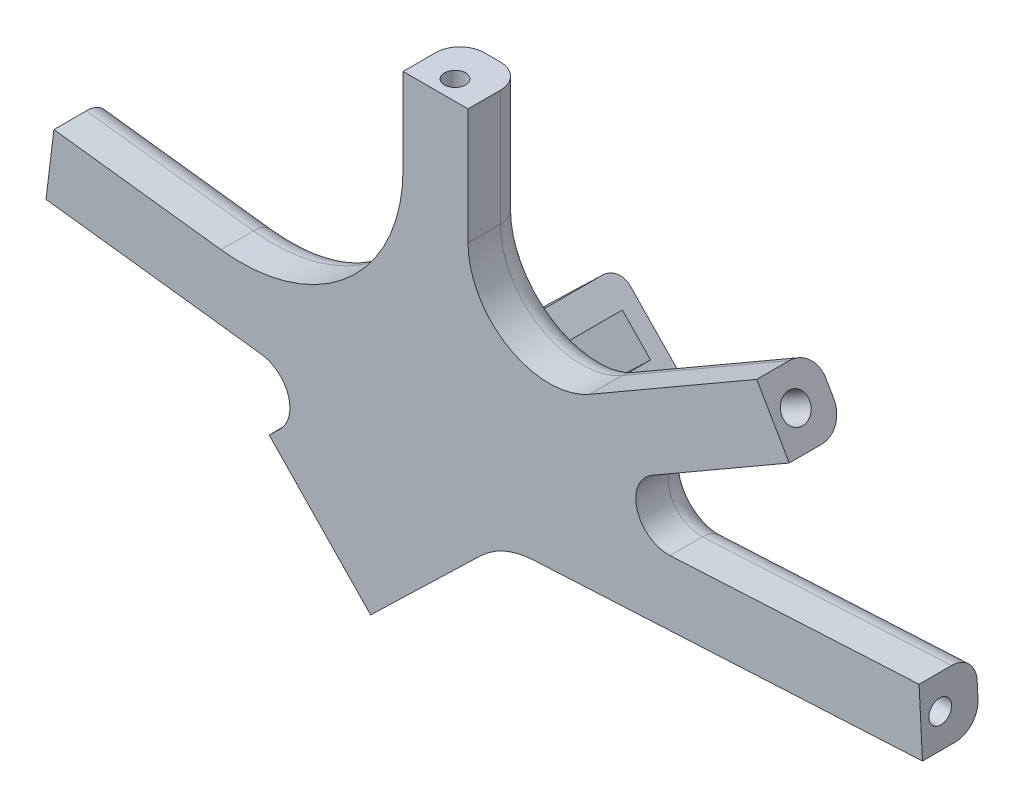
SolidWorks part; units mm, degrees
ref_plane "前基準面" through (0, 0, 0) normal (0, 0, 1) x (1, 0, 0)
ref_plane "上基準面" through (0, 0, 0) normal (0, 1, 0) x (1, 0, 0)
ref_plane "右基準面" through (0, 0, 0) normal (1, 0, 0) x (0, 0, -1)
sketch "草圖1" plane through (0, 0, 0) normal (0, 0, 1) x (1, 0, 0)
  line L0 (-27, 0) -> (-10.6362, 0) construction
  line L1 (-27, 3.1712) -> (-9.5687, 1.0309)
  line L2 (1.1225, -1.1562) -> (27, 0.2)
  line L3 (-27, 3.1712) -> (-26.5125, 7.1414)
  line L4 (-26.5125, 7.1414) -> (-5, 4.5)
  line L5 (3.1228, 2.9541) -> (26.7907, 4.1945)
  line L6 (26.7907, 4.1945) -> (27, 0.2)
  line L7 (-1, 5.1927) -> (16.7907, 15.4641)
  line L8 (16.7907, 15.4641) -> (18.7907, 12)
  line L9 (18.7907, 12) -> (3.1228, 2.9541)
  line L10 (-5, 4.5) -> (-5, 21)
  line L11 (-5, 21) -> (-1, 21)
  line L12 (-1, 21) -> (-1, 5.1927)
  line L13 (-9.5687, 1.0309) -> (-13.2519, -2.5259)
  line L14 (-13.2519, -2.5259) -> (-7, -9)
  line L15 (-7, -9) -> (1.1225, -1.1562)
  line L17 (2.3198, 0) -> (27, 0) construction
  point P19 (-10.6362, 0)
  dimension "D1" = 54
  dimension "D2" = 27
  dimension "D3" = 7
  dimension "D4" = 3
  dimension "D5" = 90
  dimension "D6" = 4
  dimension "D7" = 4
  dimension "D8" = 4.5
  dimension "D9" = 4
  dimension "D10" = 30
  dimension "D11" = 8
  dimension "D12" = 12
  dimension "D13" = 4
  dimension "D14" = 22
  dimension "D15" = 136
  dimension "D16" = 90
  dimension "D17" = 9
  dimension "D18" = 20
  dimension "D19" = 16.5
  dimension "D20" = 0.2
  dimension "D21" = 9
extrude "填料-伸長1" add sketch "草圖1" along normal blind 3.5
fillet "圓角1" radius 5 2 edges at (1.1225, -1.1562, 1.75) (-1, 5.1927, 1.75)
fillet "圓角2" radius 2 2 edges at (-9.5687, 1.0309, 1.75) (3.1228, 2.9541, 1.75)
fillet "圓角3" radius 10 1 edges at (-5, 4.5, 1.75)
sketch "草圖2" plane through (-26.9826, 3.313, 0) normal (-0.9925, 0.1219, 0) x (0, 0, 1)
  line L0 (3.5, 3.8571) -> (0, 3.8571) construction
  line L1 (3.5, 3.8571) -> (3.5, -0.1429) construction
  circle A0 centre (2.3, 1.8571) radius 0.65
  dimension "D1" = 1.3
  dimension "D2" = 2
  dimension "D3" = 1.2
extrude "除料-伸長1" cut sketch "草圖2" against normal blind 20
sketch "草圖3" plane through (0, 21, 0) normal (0, 1, 0) x (1, 0, 0)
  line L0 (-1, -3.5) -> (-1, 0) construction
  line L1 (-1, -3.5) -> (-5, -3.5) construction
  circle A0 centre (-3, -2.3) radius 0.65
  dimension "D2" = 1.3
  dimension "D1" = 2
  dimension "D3" = 1.2
extrude "除料-伸長2" cut sketch "草圖3" against normal blind 20
sketch "草圖4" plane through (19.2891, 11.1366, 0) normal (0.866, 0.5, 0) x (0, 0, -1)
  line L0 (-3.5, 4.997) -> (0, 4.997) construction
  line L1 (-3.5, 0.997) -> (-3.5, 4.997) construction
  circle A0 centre (-2.1, 2.997) radius 0.85
  point P2 (-1.75, 4.997)
  dimension "D2" = 1.7
  dimension "D1" = 2
  dimension "D3" = 1.4
extrude "除料-伸長3" cut sketch "草圖4" against normal blind 20
sketch "草圖5" plane through (26.9365, 1.4117, 0) normal (0.9986, 0.0523, 0) x (0, 0, -1)
  line L0 (0, 2.7867) -> (-3.5, 2.7867) construction
  line L1 (-3.5, -1.2133) -> (-3.5, 2.7867) construction
  circle A0 centre (-2.3, 0.7867) radius 0.7
  dimension "D2" = 1.4
  dimension "D1" = 2
  dimension "D3" = 1.2
extrude "除料-伸長4" cut sketch "草圖5" against normal blind 20
sketch "草圖6" plane through (0, 0, 0) normal (0, 0, -1) x (-1, 0, 0)
  line L0 (8.042, -7.921) -> (12.5573, -3.2453)
  line L1 (13.2519, -2.5259) -> (7, -9) construction
  line L2 (12.5573, -3.2453) -> (3.2058, 5.7853)
  line L3 (3.2058, 5.7853) -> (-1.3094, 1.1096)
  line L4 (-1.3094, 1.1096) -> (8.042, -7.921)
  line L6 (7, -9) -> (0.2222, -2.4548) construction
  line M17 (7, -9) -> (13.2519, -2.5259)
  dimension "D1" = 6.5
  dimension "D2" = 13
  dimension "D3" = 1.5
extrude "填料-伸長2" add sketch "草圖6" along normal blind 8 contours L3 L4 L2 M17 region at (-5.6239, -1.0679, 0)
sketch "草圖7" plane through (0.0774, -0.0802, 0) normal (0.6947, -0.7193, 0) x (0, 0, -1)
  line L0 (8, -11.2873) -> (0, -11.2873) construction
  circle A0 centre (4, -8.7873) radius 1
  circle A2 centre (4, -0.7873) radius 1
  dimension "D1" = 2
  dimension "D6" = 2
  dimension "D2" = 2.5
  dimension "D3" = 4
  dimension "D4" = 8
extrude "除料-伸長6" cut sketch "草圖7" against normal up to next
fillet "圓角5" radius 1.5 15 edges at (-12.9184, -2.2039, 0) (-12.0776, 0.1915, 0) (-21.3656, 6.5094, 0) (-5, 18.4015, 0) (-1, 17.4265, 0) (1.5, 9.5228, 0) (14.564, 9.5597, 0) (9.4196, 4.8194, 0) (-3.6111, -5.7274, 0) (1.2573, -1.4662, 0) (-20.3653, 2.3566, 0) (-8.3738, 8.3134, 0) (11.6453, 12.4934, 0) (19.1163, 3.7923, 0) (14.9947, -0.4292, 0)
sketch "草圖9" plane through (-8.1194, -7.8408, 0) normal (-0.7193, -0.6947, 0) x (0, 0, 1)
  line L1 (-7, 4.6386) -> (0, 4.6386)
  line L2 (-7, 4.6386) -> (-7, 2.1386)
  line L3 (-7, 2.1386) -> (0, 2.1386)
  line L4 (0, 4.6386) -> (0, 2.1386)
  line L5 (-7, 4.6386) -> (0, 2.1386) construction
  line L6 (-7, 2.1386) -> (0, 4.6386) construction
  line L7 (-8, 6.3886) -> (0, 6.3886) construction
  point P0 (-3.5, 3.3886)
  dimension "D1" = 2.5
  dimension "D2" = 7
  dimension "D3" = 7
  dimension "D4" = 1.75
extrude "除料-伸長8" cut sketch "草圖9" against normal blind 15
fillet "圓角6" radius 1 2 edges at (-3.3663, -3.4057, -8) (-7.8816, 1.27, -8)
sketch "草圖10" plane through (0.0774, -0.0802, 0) normal (0.6947, -0.7193, 0) x (0.7193, 0.6947, 0)
  line L1 (-12.2873, -1.25) -> (-10.2873, -1.25)
  line L2 (-12.2873, -1.25) -> (-12.2873, -6.75)
  line L3 (-12.2873, -6.75) -> (-10.2873, -6.75)
  line L4 (-10.2873, -1.25) -> (-10.2873, -6.75)
  line L5 (-12.2873, -1.25) -> (-10.2873, -6.75) construction
  line L6 (-12.2873, -6.75) -> (-10.2873, -1.25) construction
  line L9 (-11.2873, -7) -> (-11.2873, 0) construction
  point P0 (-11.2873, -4)
  dimension "D1" = 4
  dimension "D2" = 2
  dimension "D3" = 5.5
extrude "除料-伸長9" cut sketch "草圖10" against normal up to next
fillet "圓角8" radius 3 2 edges at (-8.1041, -6.4171, -6.75) (-8.1041, -6.4171, -1.25)
sketch "草圖11" plane through (0, 0, 0) normal (0, 0, -1) x (-1, 0, 0)
  text T0 "L" font "Microsoft YaHei UI" height 6
extrude "除料-伸長10" cut sketch "草圖11" against normal blind 0.6
